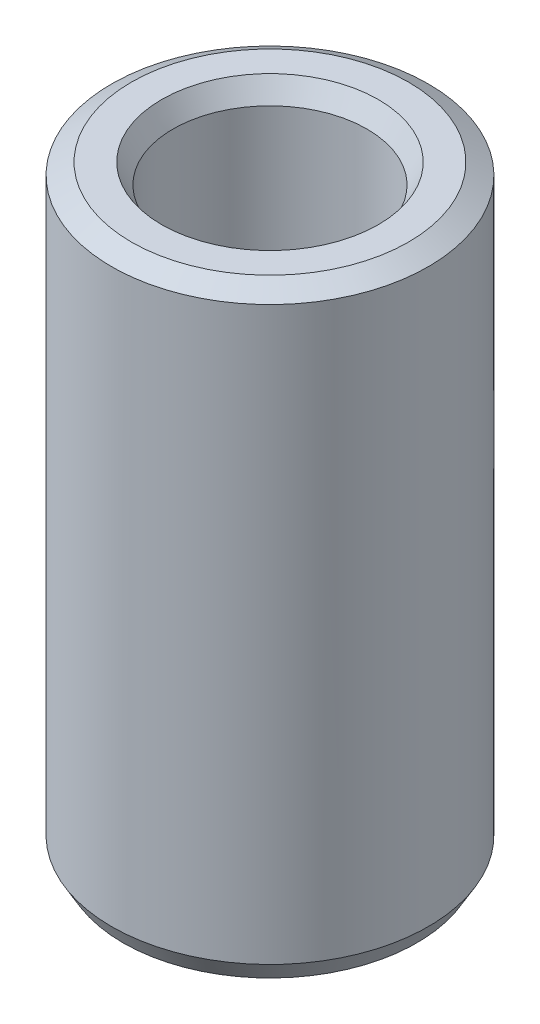
SolidWorks part; units mm, degrees
ref_plane "Front Plane" through (0, 0, 0) normal (0, 0, 1) x (1, 0, 0)
ref_plane "Top Plane" through (0, 0, 0) normal (0, 1, 0) x (1, 0, 0)
ref_plane "Right Plane" through (0, 0, 0) normal (1, 0, 0) x (0, 0, -1)
sketch "Sketch1" plane through (0, 0, 0) normal (0, 1, 0) x (1, 0, 0)
  circle A0 centre (0, 0) radius 35
  dimension "SLEEVE_OD" = 70
extrude "Boss-Extrude1" add sketch "Sketch1" along normal blind 133.2176
sketch "Sketch2" plane through (0, 0, 0) normal (0, 1, 0) x (1, 0, 0)
  circle A0 centre (0, 0) radius 21.4299
  dimension "BORE_D" = 42.8598
extrude "Cut-Extrude1" cut sketch "Sketch2" along normal through all
chamfer "Chamfer1" distance 2.5263 angle 60 4 edges at (0, 133.2176, 21.4299) (0, 0, 21.4299) (0, 0, 35) (0, 133.2176, 35) first distance on face at (0, 133.2176, 21.4299) first distance on face at (0, 0, 21.4299) first distance on face at (0, 133.2176, 35)
